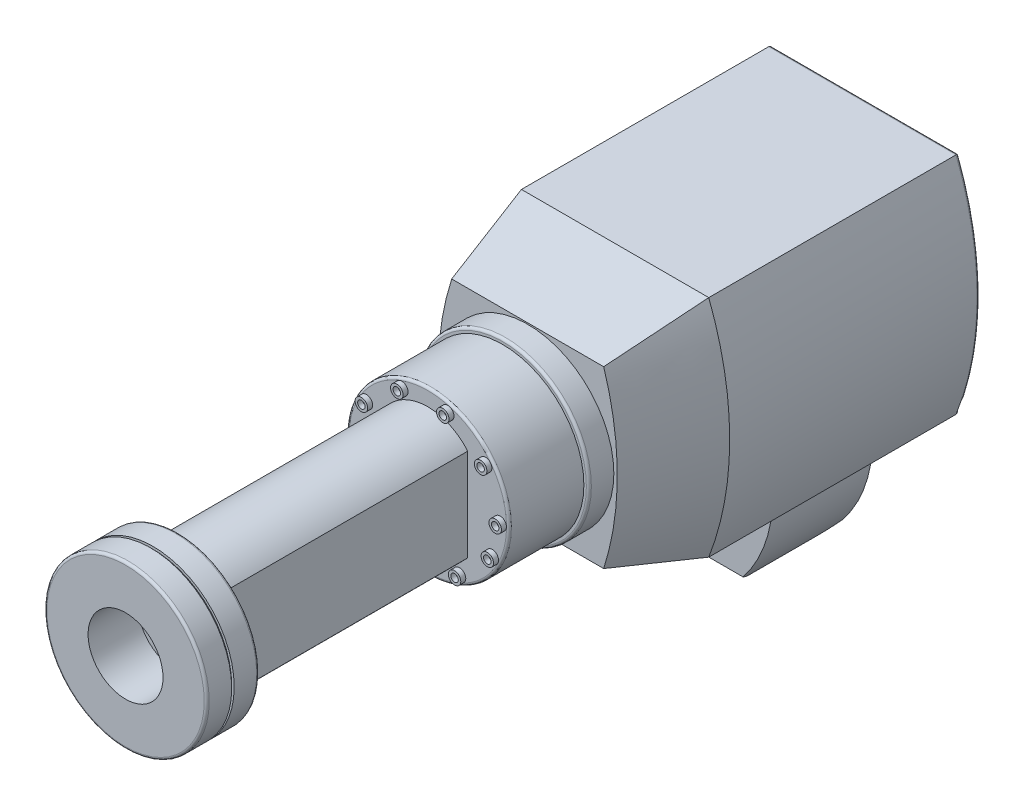
SolidWorks part; units mm, degrees
ref_plane "Alzado" through (0, 0, 0) normal (0, 0, 1) x (1, 0, 0)
ref_plane "Planta" through (0, 0, 0) normal (0, 1, 0) x (1, 0, 0)
ref_plane "Vista lateral" through (0, 0, 0) normal (1, 0, 0) x (0, 0, -1)
sketch "Croquis1" plane through (0, 0, 0) normal (0, 0, 1) x (1, 0, 0)
  line L0 (0, 0) -> (0, 45) construction
  line L1 (0, 0) -> (0, -45) construction
  line L2 (37.5, 45) -> (-37.5, 45)
  line L3 (37.5, -45) -> (-37.5, -45)
  arc A0 (-37.5, 45) -> (-37.5, -45) centre (79.119, 0) ccw
  arc A1 (37.5, 45) -> (37.5, -45) centre (-79.119, 0) cw
  point P7 (0, 45)
  point P10 (0, -45)
  dimension "D4" = 125
  dimension "D1" = 45
  dimension "D2" = 75
  dimension "D3" = 75
extrude "Saliente-Extruir1" add sketch "Croquis1" along normal blind 100
sketch "Croquis2" plane through (0, 0, 100) normal (0, 0, 1) x (1, 0, 0)
  line L2 (-37.5, -45) -> (37.5, -45)
  line L3 (37.5, 45) -> (-37.5, 45)
  line L4 (-37.5, -45) -> (37.5, -45)
  line L5 (37.5, 45) -> (-37.5, 45)
  arc A2 (-37.5, 45) -> (-37.5, -45) centre (79.119, 0) ccw
  arc A3 (37.5, -45) -> (37.5, 45) centre (-79.119, 0) ccw
  arc A4 (-37.5, 45) -> (-37.5, -45) centre (79.119, 0) ccw
  arc A5 (37.5, -45) -> (37.5, 45) centre (-79.119, 0) ccw
  dimension "D1" = 0
ref_plane "Plano1" through (0, 0, 135) normal (0, 0, 1) x (1, 0, 0)
sketch "Croquis3" plane through (0, 0, 135) normal (0, 0, 1) x (1, 0, 0)
  line L4 (30.4255, 35) -> (-30.4255, 35)
  line L5 (-30.4255, -35) -> (30.4255, -35)
  line L6 (30.4255, 35) -> (-30.4255, 35)
  line L7 (-30.4255, -35) -> (30.4255, -35)
  arc A4 (30.4255, -35) -> (30.4255, 35) centre (-79.119, 0) ccw
  arc A5 (-30.4255, 35) -> (-30.4255, -35) centre (79.119, 0) ccw
  arc A6 (30.4255, -35) -> (30.4255, 35) centre (-79.119, 0) ccw
  arc A7 (-30.4255, 35) -> (-30.4255, -35) centre (79.119, 0) ccw
  dimension "D1" = 10
loft "Recubrir1" add profiles "Croquis3", "Croquis2" connector at (-30.4255, 35, 135) connector at (-37.5, 45, 100)
sketch "Croquis4" plane through (0, 0, 135) normal (0, 0, 1) x (1, 0, 0)
  circle A0 centre (0, 0) radius 34.5
  dimension "D1" = 69
extrude "Saliente-Extruir2" add sketch "Croquis4" along normal blind 10
sketch "Croquis6" plane through (0, 0, 145) normal (0, 0, 1) x (1, 0, 0)
  circle A2 centre (0, 0) radius 32.5
  circle A3 centre (0, 0) radius 32.5
  dimension "D1" = 2
extrude "Saliente-Extruir4" add sketch "Croquis6" along normal blind 30
sketch "Croquis7" plane through (0, 0, 175) normal (0, 0, 1) x (1, 0, 0)
  line L0 (0, 0) -> (29, 0) construction
  circle A0 centre (29, 0) radius 2.5
  circle A1 centre (29, 0) radius 1.5
  dimension "D2" = 5
  dimension "D1" = 29
  dimension "D3" = 1
extrude "Saliente-Extruir5" add sketch "Croquis7" along normal blind 2
pattern_circular "MatrizC1" count 10 every 37 about axis through (0, 0, 175) along (0, 0, 1) of "Saliente-Extruir5"
sketch "Croquis8" plane through (0, 0, 175) normal (0, 0, 1) x (1, 0, 0)
  line L0 (0, 0) -> (16, 0) construction
  line L1 (16, -18.5) -> (16, 18.5)
  line L2 (0, 0) -> (0, -17.1538) construction
  line L3 (-16, -18.5) -> (-16, 18.5)
  arc A0 (-16, 18.5) -> (16, 18.5) centre (0, 4.8985) cw
  arc A1 (-16, -18.5) -> (16, -18.5) centre (0, -4.8985) ccw
  point P6 (16, 0)
  dimension "D3" = 21
  dimension "D1" = 16
  dimension "D2" = 37
extrude "Saliente-Extruir6" add sketch "Croquis8" along normal blind 100
sketch "Croquis9" plane through (0, 0, 275) normal (0, 0, 1) x (1, 0, 0)
  circle A0 centre (0, 0) radius 32.5 construction
  circle A1 centre (0, 0) radius 32.5
extrude "Saliente-Extruir7" add sketch "Croquis9" along normal blind 10
sketch "Croquis10" plane through (0, 0, 285) normal (0, 0, 1) x (1, 0, 0)
  circle A2 centre (0, 0) radius 31.5
  circle A3 centre (0, 0) radius 31.5
  dimension "D1" = 1
extrude "Saliente-Extruir8" add sketch "Croquis10" along normal blind 1
sketch "Croquis11" plane through (0, 0, 286) normal (0, 0, 1) x (1, 0, 0)
  circle A0 centre (0, 0) radius 32.5 construction
  circle A1 centre (0, 0) radius 32.5
extrude "Saliente-Extruir9" add sketch "Croquis11" along normal blind 10
ref_plane "Plano2" through (-37.5, 0, 0) normal (1, 0, 0) x (0, 0, -1)
sketch "Croquis12" plane through (-37.5, 0, 0) normal (1, 0, 0) x (0, 0, -1)
  line L0 (-100, -45) -> (0, -45) construction
  circle A0 centre (-50, -45) radius 42.5
  dimension "D1" = 85
extrude "Saliente-Extruir10" add sketch "Croquis12" along normal mid plane 21
sketch "Croquis13" plane through (-27, 0, 0) normal (1, 0, 0) x (0, 0, -1)
  line L0 (-50, -45) -> (-50, -75) construction
  line L1 (-100, -45) -> (0, -45) construction
  line L2 (-70, -45) -> (-70, -75)
  line L3 (-30, -45) -> (-30, -75)
  line L4 (-92.5, -45) -> (-7.5, -45) construction
  line L5 (-70, -45) -> (-30, -45)
  arc A0 (-70, -75) -> (-30, -75) centre (-50, -52.6393) ccw
  dimension "D4" = 30
  dimension "D1" = 30
  dimension "D2" = 20
  dimension "D3" = 20
extrude "Saliente-Extruir11" add sketch "Croquis13" along normal blind 35
ref_plane "Plano3" through (0, 0, 50) normal (0, 0, 1) x (1, 0, 0)
sketch "Croquis14" plane through (0, 0, 50) normal (0, 0, 1) x (1, 0, 0)
  line L0 (8, -45) -> (8, -87)
  line L1 (8, -45) -> (33, -45)
  line L2 (-37.5, -45) -> (37.5, -45) construction
  arc A0 (33, -45) -> (8, -87) centre (-21.8393, -40.7981) cw
  dimension "D3" = 55
  dimension "D1" = 42
  dimension "D2" = 25
extrude "Saliente-Extruir12" add sketch "Croquis14" along normal mid plane 40
sketch "Croquis15" plane through (8, 0, 0) normal (-1, 0, 0) x (0, 0, 1)
  line L3 (70, -87) -> (70, -75)
  line L4 (30, -75) -> (30, -87)
  line L5 (30, -87) -> (70, -87)
  line L6 (70, -87) -> (70, -75)
  line L7 (30, -75) -> (30, -87)
  line L8 (30, -87) -> (70, -87)
  arc A1 (30, -75) -> (70, -75) centre (50, -52.6393) ccw
  arc A2 (30, -75) -> (70, -75) centre (50, -52.6393) ccw
  dimension "D1" = 0
extrude "Cortar-Extruir1" cut sketch "Croquis15" against normal blind 40
fillet "Redondeo1" radius 1 4 edges at (0, -45, 0) (45.881, 0, 0) (0, 45, 0) (-45.881, 0, 0)
fillet "Redondeo2" radius 1 2 edges at (-48, -45, 7.5) (-27, -87.5, 50)
fillet "Redondeo3" radius 1 2 edges at (32.5, 0, 175) (34.5, 0, 145)
fillet "Redondeo4" radius 1 2 edges at (32.5, 0, 275) (32.5, 0, 296)
sketch "Croquis16" plane through (0, 0, 296) normal (0, 0, 1) x (1, 0, 0)
  circle A0 centre (0, 0) radius 15
  dimension "D1" = 30
extrude "Cortar-Extruir2" cut sketch "Croquis16" against normal blind 20
sketch "Croquis17" plane through (-48, 0, 0) normal (-1, 0, 0) x (0, 0, 1)
  circle A0 centre (50, -45) radius 15
  dimension "D1" = 30
extrude "Cortar-Extruir3" cut sketch "Croquis17" against normal blind 20
